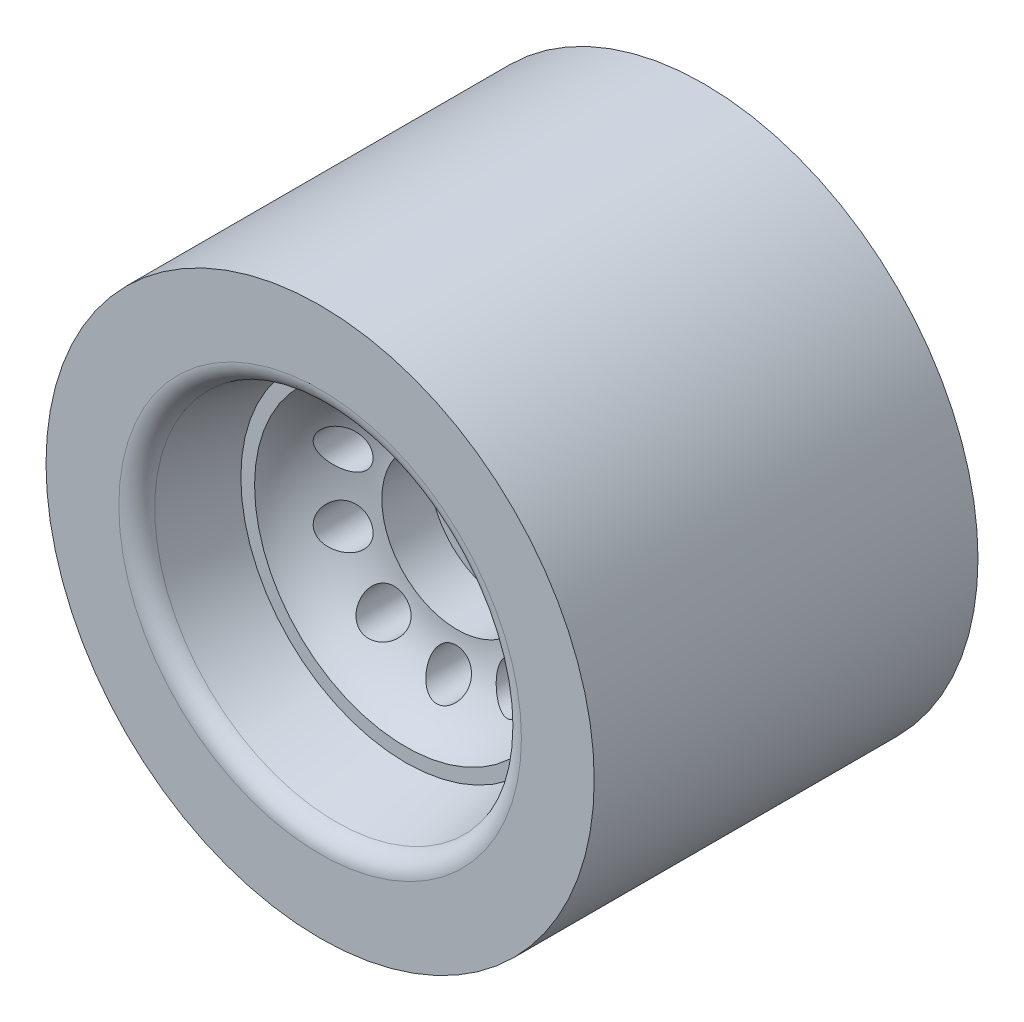
SolidWorks part; units mm, degrees
material "폴리우레탄(11671)"
ref_plane "정면" through (0, 0, 0) normal (0, 0, 1) x (1, 0, 0)
ref_plane "윗면" through (0, 0, 0) normal (0, 1, 0) x (1, 0, 0)
ref_plane "우측면" through (0, 0, 0) normal (1, 0, 0) x (0, 0, -1)
sketch "스케치1" plane through (0, 0, 0) normal (0, 0, 1) x (1, 0, 0)
  circle A0 centre (0, 0) radius 40
  dimension "D1" = 80
extrude "보스-돌출1" add sketch "스케치1" along normal mid plane 56
sketch "스케치2" plane through (0, 0, 28) normal (0, 0, 1) x (1, 0, 0)
  circle A0 centre (0, 0) radius 5
  dimension "D1" = 10
extrude "컷-돌출1" cut sketch "스케치2" against normal through all
sketch "스케치4" plane through (0, 0, 0) normal (1, 0, 0) x (0, 0, -1)
  line L0 (28, 0) -> (-28, 0) construction
  line L1 (28, -40) -> (28, 40) construction
  line L2 (-28, 40) -> (-28, -40) construction
  line L3 (0, 0) -> (0, -40) construction
  line L4 (-28, -40) -> (28, -40) construction
  line L5 (28, 40) -> (26.6, 33.9)
  line L6 (28.1584, 34.5) -> (28.1584, 0) construction
  line L7 (14.4, 0) -> (28, 0)
  line L8 (14.4, 0) -> (14.4, 11)
  line L9 (26.6, 33.9) -> (25.6, 33.4)
  line L10 (28, 0) -> (28, 40)
  line L11 (-28, 0) -> (-28, 27)
  line L12 (-28, 27) -> (-15.5084, 24.06)
  line L13 (-8, 11) -> (-8, 0)
  line L14 (-8, 0) -> (-28, 0)
  line L15 (-15.5084, 24.06) -> (-15.5084, 22.06)
  arc A0 (21.9084, 22.06) -> (23.9067, 28.6555) centre (42.9172, 19.295) cw
  arc A1 (14.4, 11) -> (21.9084, 22.06) centre (26.3, 11) cw
  arc A2 (23.9067, 28.6555) -> (25.6, 33.4) centre (4.1696, 38.3738) ccw
  arc A3 (-15.5084, 22.06) -> (-8, 11) centre (-19.9, 11) cw
  dimension "D5" = 11.9
  dimension "D4" = 0.5
  dimension "D10" = 6.25
  dimension "D11" = 12.44
  dimension "D9" = 21.19
  dimension "D12" = 22
  dimension "D14" = 13
  dimension "D13" = 11.9
  dimension "D2" = 22.06
  dimension "D3" = 6.1
  dimension "D6" = 11
  dimension "D7" = 12.2
  dimension "D8" = 1
  dimension "D15" = 20
  dimension "D16" = 2
  dimension "D17" = 1.4
revolve "컷-회전1" cut sketch "스케치4" angle 360 about L0
sketch "스케치5" plane through (0, 0, 0) normal (0, 0, 1) x (1, 0, 0)
  line L0 (0, 0) -> (0, 40) construction
  circle A0 centre (0, 0) radius 40 construction
  circle A1 centre (0, 15.875) radius 3
  dimension "D1" = 6
  dimension "D2" = 15.875
extrude "컷-돌출2" cut sketch "스케치5" against normal through all both and the other way through all
pattern_circular "원형 패턴1" count 10 over 360 about axis through (0, 0, -28) along (0, 0, 1) of "컷-돌출2"
fillet "필렛1" radius 3 1 edges at (-27, 0, 28)
sketch "스케치6" plane through (0, 0, 8) normal (0, 0, 1) x (1, 0, 0)
  circle A0 centre (0, 0) radius 11
  dimension "D1" = 22
extrude "컷-돌출3" cut sketch "스케치6" against normal blind 7
sketch "스케치7" plane through (0, 0, -14.4) normal (0, 0, -1) x (-1, 0, 0)
  circle A0 centre (0, 0) radius 11
  dimension "D1" = 22
extrude "컷-돌출4" cut sketch "스케치7" against normal blind 7
